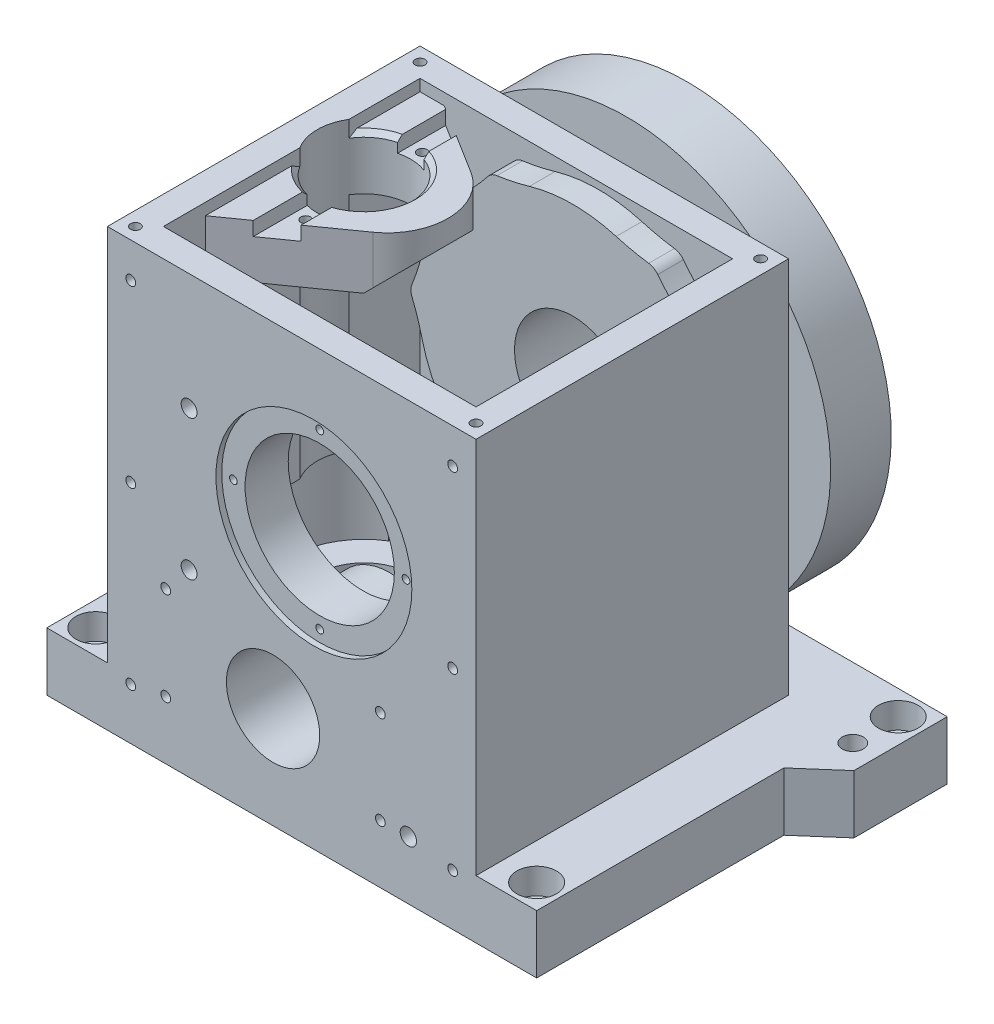
SolidWorks part; units mm, degrees
material "Ductile Iron"
ref_plane "Front Plane" through (0, 0, 0) normal (0, 0, 1) x (1, 0, 0)
ref_plane "Top Plane" through (0, 0, 0) normal (0, 1, 0) x (1, 0, 0)
ref_plane "Right Plane" through (0, 0, 0) normal (1, 0, 0) x (0, 0, -1)
sketch "Sketch1" plane through (0, 0, 0) normal (0, 0, 1) x (1, 0, 0)
  line L1 (79, -93.5) -> (-79, -93.5)
  line L2 (79, -93.5) -> (79, 93.5)
  line L3 (79, 93.5) -> (-79, 93.5)
  line L4 (-79, -93.5) -> (-79, 93.5)
  line L5 (79, -93.5) -> (-79, 93.5) construction
  line L6 (79, 93.5) -> (-79, -93.5) construction
  point P0 (0, 0)
  dimension "D1" = 158
  dimension "D2" = 187
extrude "Extrude1" add sketch "Sketch1" along normal blind 134
shell "Shell1" thickness 12 removed face at (0, 93.5, 67)
sketch "Sketch2" plane through (0, 0, 0) normal (0, 0, -1) x (-1, 0, 0)
  line L0 (-79, 93.5) -> (79, 93.5) construction
  line L1 (-79, -93.5) -> (-79, 93.5) construction
  circle A0 centre (-9.5, 24) radius 87.5
  dimension "D1" = 18
  dimension "D2" = 18
  dimension "D3" = 175
extrude "Extrude2" add sketch "Sketch2" along normal blind 26
sketch "Sketch3" plane through (0, 0, -26) normal (0, 0, -1) x (-1, 0, 0)
  circle A0 centre (-9.5, 24) radius 82.5
  circle A1 centre (-9.5, 24) radius 87.5 construction
  dimension "D1" = 5
extrude "Extrude4" cut sketch "Sketch3" against normal blind 11
sketch "Sketch4" plane through (0, 0, -15) normal (0, 0, -1) x (-1, 0, 0)
  circle A0 centre (-9.5, 24) radius 75.5
  circle A1 centre (-9.5, 24) radius 87.5 construction
  dimension "D1" = 12
extrude "Extrude5" cut sketch "Sketch4" against normal blind 5
sketch "Sketch5" plane through (0, 0, -10) normal (0, 0, -1) x (-1, 0, 0)
  circle A0 centre (-9.5, 24) radius 57
  dimension "D1" = 114
extrude "Extrude6" add sketch "Sketch5" along normal blind 18
sketch "Sketch6" plane through (0, 0, -28) normal (0, 0, -1) x (-1, 0, 0)
  circle A0 centre (-9.5, 24) radius 25
  dimension "D1" = 50
extrude "Extrude7" cut sketch "Sketch6" against normal blind 109
sketch "Sketch8" plane through (0, 0, 134) normal (0, 0, 1) x (1, 0, 0)
  circle A0 centre (9.5, 24) radius 32
  circle A1 centre (9.5, 24) radius 25 construction
  dimension "D1" = 64
extrude "Extrude8" cut sketch "Sketch8" against normal blind 109
sketch "Sketch41" plane through (0, 0, 122) normal (0, 0, -1) x (-1, 0, 0)
  circle A0 centre (-9.5, 24) radius 41
  circle A1 centre (-9.5, 24) radius 32 construction
  circle A2 centre (-9.5, 24) radius 32
  circle A3 centre (-9.5, 24) radius 32 construction
  dimension "D1" = 9
extrude "Extrude42" add sketch "Sketch41" along normal blind 9
sketch "Sketch9" plane through (0, 0, 134) normal (0, 0, 1) x (1, 0, 0)
  circle A0 centre (9.5, 24) radius 42
  circle A1 centre (9.5, 24) radius 32 construction
  dimension "D1" = 10
extrude "Extrude9" cut sketch "Sketch9" against normal blind 2.5
hole_wizard "M5 Tapped Hole7" positions "Sketch60" profile "Sketch59" tap size "M5" standard "ISO"
sketch "Sketch60" plane through (0, 0, -10) normal (0, 0, -1) x (-1, 0, 0)
  line L0 (-9.5, 99.5) -> (-9.5, -51.5) construction
  line L2 (-9.5, 24) -> (66, 24) construction
  line L4 (-9.5, 24) -> (-72.9, 24) construction
  circle A0 centre (-9.5, 24) radius 75.5 construction
  circle A1 centre (-9.5, 24) radius 75.5 construction
  circle A2 centre (-9.5, 24) radius 57 construction
  point P0 (-72.9, 24)
  dimension "D1" = 6.4
sketch "Sketch59" plane through (72.9, 24, -10) normal (1, 0, 0) x (0, 1, 0)
  line L0 (0, 0) -> (0, 23.2618)
  line L1 (0, 23.2618) -> (2.1, 22)
  line L2 (2.1, 22) -> (2.1, 0)
  line L5 (2.1, 0) -> (0, 0)
  line L10 (0, 23.2618) -> (-2.1, 22) construction
  line L11 (0, -6.35) -> (0, 107.95) construction
  dimension "Tap Drill Dia." = 4.2
  dimension "Tap Drill Depth" = 22
  dimension "Drill Angle" = 118
cosmetic thread "Hole Thread10" parameters "D1"=18, "D2"=5
pattern_circular "CirPattern7" count 6 every 60 about axis through (9.5, 24, -28) along (0, 0, -1) of "M5 Tapped Hole7"
sketch "Sketch10" plane through (0, 0, 134) normal (0, 0, 1) x (1, 0, 0)
  line L0 (-79, 93.5) -> (-79, -93.5) construction
  line L1 (-79, -93.5) -> (79, -93.5) construction
  circle A0 centre (-8, -50) radius 20
  dimension "D1" = 51
  dimension "D2" = 23.5
  dimension "D3" = 40
extrude "Extrude10" cut sketch "Sketch10" against normal blind 135.5
sketch "Sketch11" plane through (0, -93.5, 0) normal (0, -1, 0) x (1, 0, 0)
  line L0 (-79, 134) -> (79, 134) construction
  line L1 (105, 134) -> (79, 134)
  line L2 (105, 134) -> (105, -26)
  line L3 (105, -26) -> (-105, -26)
  line L4 (-105, 134) -> (-105, -26)
  line L5 (0, 0) -> (0, 134) construction
  line L7 (79, 0) -> (-79, 0)
  line L8 (79, 134) -> (79, 0)
  line L9 (-79, 0) -> (-79, 134)
  line L13 (79, 134) -> (79, 0) construction
  line L14 (-79, 134) -> (-105, 134)
  dimension "D1" = 210
  dimension "D2" = 160
  dimension "D3" = 26
extrude "Extrude12" add sketch "Sketch11" against normal blind 25
sketch "Sketch12" plane through (0, 0, -26) normal (0, 0, -1) x (-1, 0, 0)
  line L0 (-43.0857, -67) -> (24.0857, -67)
  arc A0 (-43.0857, -67) -> (24.0857, -67) centre (-9.5, 24) ccw
  dimension "D2" = 194
  dimension "D1" = 6
extrude "Extrude13" cut sketch "Sketch12" against normal up to surface (26 mm away) up to face at (-57.6084, -2.2759, 0)
sketch "Sketch13" plane through (0, 0, -28) normal (0, 0, -1) x (-1, 0, 0)
  line L0 (-9.5, 24) -> (-9.5, 88.8285) construction
  line L1 (-55, 24) -> (36, 24) construction
  line L3 (-56.5, 38.5) -> (-53.5, 38.5)
  line L4 (-56.5, 38.5) -> (-56.5, 32.3666)
  line L6 (-53.5, 38.5) -> (-53.5, 32.3666)
  arc A0 (-56.5, 32.3666) -> (-53.5, 32.3666) centre (-55, 24) ccw
  point P10 (-55, 38.5)
  dimension "D2" = 17
  dimension "D1" = 91
  dimension "D3" = 6
  dimension "D4" = 3
extrude "Extrude14" cut sketch "Sketch13" against normal blind 45
pattern_circular "CirPattern1" count 2 every 180 about axis through (9.5, 24, -28) along (0, 0, -1) of "Extrude14"
sketch "Sketch16" plane through (0, 0, -28) normal (0, 0, -1) x (-1, 0, 0)
  line L0 (-9.5, 81) -> (-9.5, 24) construction
  line L1 (-9.5, 24) -> (-40.5, 24) construction
  circle A0 centre (-40.5, 24) radius 4
  circle A1 centre (-9.5, 24) radius 57 construction
  circle A2 centre (-9.5, 24) radius 57 construction
  circle A6 centre (-9.5, 24) radius 25 construction
  dimension "D1" = 8
  dimension "D2" = 6
extrude "Extrude15" cut sketch "Sketch16" against normal blind 45
pattern_circular "CirPattern2" count 6 every 60 about axis through (9.5, 24, -28) along (0, 0, -1) of "Extrude15"
sketch "Sketch17" plane through (0, 0, -10) normal (0, 0, -1) x (-1, 0, 0)
  line L0 (-9.5, 24) -> (-106.9282, 24) construction
  line L1 (-9.5, 24) -> (-63.1936, 55) construction
  circle A0 centre (-63.1936, 55) radius 4
  circle A1 centre (-9.5, 24) radius 57 construction
  dimension "D2" = 8
  dimension "D3" = 1
  dimension "D1" = 30
extrude "Extrude16" cut sketch "Sketch17" against normal blind 21
sketch "Sketch18" plane through (0, 0, -10) normal (0, 0, -1) x (-1, 0, 0)
  line L0 (-9.5, 81) -> (-9.5, 24) construction
  line L1 (-9.5, 24) -> (-63.1936, -7) construction
  circle A0 centre (-9.5, 24) radius 57 construction
  circle A1 centre (-9.5, 24) radius 57 construction
  circle A2 centre (-63.1936, -7) radius 3
  dimension "D2" = 6
  dimension "D3" = 2
  dimension "D1" = 120
extrude "Extrude17" cut sketch "Sketch18" against normal blind 9
pattern_circular "CirPattern3" count 2 every 180 about axis through (9.5, 24, 81) along (0, 0, -1) of "Extrude16"
pattern_circular "CirPattern4" count 2 every 180 about axis through (9.5, 24, 81) along (0, 0, -1) of "Extrude17"
sketch "Sketch19" plane through (0, -68.5, 0) normal (0, 1, 0) x (1, 0, 0)
  line L0 (105, -28) -> (105, 26)
  line L1 (105, 26) -> (121, 26)
  line L2 (121, 26) -> (121, -14)
  line L3 (121, -14) -> (105, -28)
  line L4 (105, 26) -> (105, -134) construction
  dimension "D1" = 16
  dimension "D2" = 54
  dimension "D3" = 40
extrude "Extrude18" add sketch "Sketch19" against normal up to surface (25 mm away) up to face at (0, -93.5, 54)
sketch "Sketch20" plane through (0, -68.5, 0) normal (0, 1, 0) x (1, 0, 0)
  line L0 (-105, 26) -> (-19.7019, 26) construction
  line L1 (-105, -134) -> (-105, 26) construction
  line L2 (-79, -134) -> (-105, -134) construction
  line L3 (105, -28) -> (105, -134) construction
  line L4 (105, -134) -> (79, -134) construction
  line L5 (38.7019, 26) -> (121, 26) construction
  line L6 (121, -14) -> (121, 26) construction
  circle A0 centre (-94.5, -123.5) radius 8.5
  circle A1 centre (-94.5, 15.5) radius 8.5
  circle A2 centre (110.5, 15.5) radius 8.5
  circle A3 centre (94.5, -123.5) radius 8.5
  dimension "D1" = 17
  dimension "D2" = 10.5
  dimension "D3" = 10.5
  dimension "D4" = 10.5
  dimension "D5" = 10.5
  dimension "D6" = 10.5
  dimension "D7" = 10.5
  dimension "D8" = 10.5
  dimension "D9" = 10.5
extrude "Extrude19" cut sketch "Sketch20" against normal blind 11
sketch "Sketch21" plane through (0, -68.5, 0) normal (0, 1, 0) x (1, 0, 0)
  line L1 (38.7019, 26) -> (121, 26) construction
  circle A0 centre (-94.5, 15.5) radius 5.5
  circle A1 centre (-94.5, -123.5) radius 5.5
  circle A2 centre (94.5, -123.5) radius 5.5
  circle A3 centre (110.5, 15.5) radius 5.5
  circle A4 centre (110.5, -4) radius 4.5
  dimension "D1" = 11
  dimension "D2" = 9
  dimension "D3" = 30
extrude "Extrude20" cut sketch "Sketch21" against normal through all
sketch "Sketch22" plane through (0, 0, 12) normal (0, 0, 1) x (1, 0, 0)
  line L1 (67, 93.5) -> (-67, 93.5) construction
  line L2 (67, 57.4066) -> (67, -9.4066)
  line L3 (67, -81.5) -> (67, 93.5) construction
  line L5 (16.6041, -81.5) -> (-32.6041, -81.5)
  line L6 (-67, -81.5) -> (67, -81.5) construction
  arc A0 (67, 57.4066) -> (47.1987, 78.7819) centre (9.5, 24) ccw
  arc A1 (-37.5071, -23.0381) -> (-32.6041, -81.5) centre (-8, -50) ccw
  arc A2 (47.1987, 78.7819) -> (38.0932, 84.039) centre (41.2, 78.906) ccw
  circle A3 centre (9.5, 24) radius 25 construction
  arc A4 (30.4583, -39.111) -> (38.0932, -36.039) centre (9.5, 24) ccw
  arc A5 (16.6041, -81.5) -> (30.4583, -39.111) centre (-8, -50) ccw
  arc A6 (38.0932, 84.039) -> (-19.0932, 84.039) centre (9.5, 24) ccw
  arc A7 (-19.0932, 84.039) -> (-28.1987, 78.7819) centre (-22.2, 78.906) ccw
  arc A8 (-28.1987, 78.7819) -> (-56.7919, 29.2571) centre (9.5, 24) ccw
  arc A9 (38.0932, -36.039) -> (47.1987, -30.7819) centre (41.2, -30.906) ccw
  arc A10 (47.1987, -30.7819) -> (67, -9.4066) centre (9.5, 24) ccw
  arc A11 (-56.7919, 29.2571) -> (-56.7919, 18.7429) centre (-53.9, 24) ccw
  arc A12 (-56.7919, 18.7429) -> (-37.5071, -23.0381) centre (9.5, 24) ccw
  dimension "D1" = 3
  dimension "D2" = 39.9701
  dimension "D3" = 6
  dimension "D4" = 12
  dimension "D5" = 12
  dimension "D6" = 12
extrude "Extrude25" add sketch "Sketch22" along normal blind 11
sketch "Sketch23" plane through (0, 0, 23) normal (0, 0, 1) x (1, 0, 0)
  circle A0 centre (-8, -50) radius 20
  circle A1 centre (-8, -50) radius 20 construction
extrude "Extrude26" cut sketch "Sketch23" against normal blind 21
sketch "Sketch24" plane through (0, 0, 12) normal (0, 0, -1) x (-1, 0, 0)
  circle A0 centre (-9.5, 24) radius 25
  circle A1 centre (-9.5, 24) radius 25 construction
extrude "Extrude27" cut sketch "Sketch24" against normal blind 74
ref_plane "Plane1" through (0, 88.5, 0) normal (0, 1, 0) x (-1, 0, 0)
sketch "Sketch25" plane through (0, 88.5, 0) normal (0, 1, 0) x (-1, 0, 0)
  line L0 (67, 104) -> (24.9671, 74.2135)
  line L1 (67, 122) -> (67, 12) construction
  line L2 (67, 104) -> (67, 63.5357)
  line L3 (26.24, 30.9396) -> (56.6045, 12)
  line L4 (-67, 12) -> (67, 12) construction
  line L5 (67, 12) -> (56.6045, 12)
  line L7 (43.6601, 0) -> (79, 0) construction
  line L8 (67, 42.4643) -> (67, 12)
  arc A0 (24.9671, 74.2135) -> (26.24, 30.9396) centre (40, 53) ccw
  arc A1 (67, 63.5357) -> (67, 42.4643) centre (50, 53) ccw
  dimension "D2" = 53
  dimension "D3" = 26
  dimension "D6" = 40
  dimension "D1" = 92
  dimension "D4" = 53
  dimension "D5" = 67.277
  dimension "D7" = 10
extrude "Extrude28" add sketch "Sketch25" against normal blind 23
ref_plane "Plane2" through (0, 0, 97) normal (0, 0, 1) x (1, 0, 0)
sketch "Sketch26" plane through (0, 0, 97) normal (0, 0, 1) x (1, 0, 0)
  line L0 (-14.3015, 78.5) -> (-44, 48.8015)
  line L1 (73.7, 88.5) -> (-73.7, 88.5) construction
  line L2 (-67, 65.5) -> (-67, -81.5) construction
  line L3 (-14.3015, 78.5) -> (-10.4023, 82.3992)
  line L4 (-10.4023, 82.3992) -> (-10.4023, 48.8015)
  line L5 (-10.4023, 48.8015) -> (-44, 48.8015)
  dimension "D1" = 45
  dimension "D2" = 10
  dimension "D3" = 23
  dimension "D4" = 42
  dimension "D5" = 33.5977
extrude "Extrude29" cut sketch "Sketch26" against normal blind 73
sketch "Sketch28" plane through (0, -93.5, 0) normal (0, -1, 0) x (1, 0, 0)
  line L0 (-50, 83) -> (-79, 83)
  line L1 (-79, 134) -> (-79, 0) construction
  line L2 (-79, 23) -> (-50, 23)
  arc A0 (-50, 23) -> (-50, 83) centre (-50, 53) ccw
  arc A1 (-79, 83) -> (-79, 23) centre (-50, 53) ccw
  arc A2 (-67, 42.4643) -> (-67, 63.5357) centre (-50, 53) ccw construction
  dimension "D4" = 60
extrude "Extrude36" add sketch "Sketch28" against normal blind 74
sketch "Sketch36" plane through (0, -19.5, 0) normal (0, 1, 0) x (1, 0, 0)
  line L0 (-50, -23) -> (-67, -23)
  line L1 (-50, -83) -> (-67, -83)
  line L3 (-67, -23) -> (-67, -83)
  line L4 (-67, -83) -> (-67, -23) construction
  arc A0 (-50, -83) -> (-50, -23) centre (-50, -53) ccw
  arc A1 (-50, -83) -> (-50, -23) centre (-50, -53) ccw construction
extrude "Extrude37" cut sketch "Sketch36" against normal blind 52
sketch "Sketch37" plane through (0, -71.5, 0) normal (0, 1, 0) x (1, 0, 0)
  line L0 (-50, -23) -> (-50, -83)
  line L2 (-67, -83) -> (-50, -83) construction
  line L3 (-50, -83) -> (-62.0473, -83)
  line L4 (-50, -23) -> (-62.0473, -23)
  line L5 (47.1987, -23) -> (67, -23) construction
  line L6 (-50, -23) -> (-67, -23) construction
  arc A0 (-62.0473, -23) -> (-62.0473, -83) centre (-50, -53) ccw
  arc A2 (-50, -83) -> (-50, -23) centre (-50, -53) ccw construction
  arc A4 (-79, -23) -> (-79, -83) centre (-50, -53) ccw construction
  dimension "D1" = 9.3967
extrude "Extrude38" cut sketch "Sketch37" along normal blind 42
sketch "Sketch38" plane through (0, 0, 134) normal (0, 0, 1) x (1, 0, 0)
  line L0 (-79, -19.5) -> (-97.6698, -38.1698)
  line L1 (-97.6698, -38.1698) -> (-97.6698, -9.9037)
  line L2 (-97.6698, -9.9037) -> (-79, -19.5)
  line L4 (-79, 93.5) -> (-79, -68.5) construction
  dimension "D1" = 45
  dimension "D2" = 62.797
  dimension "D3" = 28.2661
extrude "Extrude39" cut sketch "Sketch38" against normal blind 154
sketch "Sketch35" plane through (0, 88.5, 0) normal (0, 1, 0) x (1, 0, 0)
  circle A0 centre (-50, -53) radius 20
  arc A2 (-67, -63.5357) -> (-67, -42.4643) centre (-50, -53) ccw construction
extrude "Extrude35" cut sketch "Sketch35" against normal blind 239
sketch "Sketch39" plane through (0, -93.5, 0) normal (0, -1, 0) x (1, 0, 0)
  circle A0 centre (-50, 53) radius 30
  dimension "D1" = 60
extrude "Extrude40" cut sketch "Sketch39" against normal blind 7
sketch "Sketch40" plane through (0, -93.5, 0) normal (0, -1, 0) x (1, 0, 0)
  line L0 (-70, 117) -> (75, 117)
  line L1 (75, 117) -> (75, 7)
  line L2 (75, 7) -> (-50, 7)
  line L3 (-50, 7) -> (-50, 13)
  line L4 (-70, 117) -> (-70, 93)
  line L5 (-70, 93) -> (-50, 93)
  line L6 (-105, -26) -> (121, -26) construction
  line L7 (105, 28) -> (105, 134) construction
  arc A0 (-50, 93) -> (-50, 13) centre (-50, 53) cw
  circle A2 centre (-50, 53) radius 30 construction
  dimension "D1" = 40
  dimension "D2" = 33
  dimension "D3" = 110
  dimension "D4" = 145
  dimension "D5" = 30
extrude "Extrude41" cut sketch "Sketch40" against normal blind 3
chamfer "Chamfer1" distance 3 angle 45 7 edges at (2.5, -90.5, 117) (75, -90.5, 62) (12.5, -90.5, 7) (-50, -90.5, 10) (-10, -90.5, 53) (-60, -90.5, 93) (-70, -90.5, 105)
sketch "Sketch42" plane through (0, 0, 122) normal (0, 0, -1) x (-1, 0, 0)
  line L0 (-17.5, -50) -> (-17.5, -81.5)
  line L1 (67, -81.5) -> (-67, -81.5) construction
  line L2 (33.5, -50) -> (33.5, -81.5)
  line L3 (33.5, -81.5) -> (-17.5, -81.5)
  arc A0 (33.5, -50) -> (-17.5, -50) centre (8, -50) ccw
  circle A1 centre (8, -50) radius 20
  circle A2 centre (8, -50) radius 20 construction
  dimension "D1" = 51
extrude "Extrude43" add sketch "Sketch42" along normal blind 38
sketch "Sketch43" plane through (0, 93.5, 0) normal (0, 1, 0) x (1, 0, 0)
  line L1 (-55, -13.0008) -> (-43, -13.0008)
  line L2 (-55, -13.0008) -> (-55, -95.4962)
  line L3 (-55, -95.4962) -> (-43, -95.4962)
  line L4 (-43, -13.0008) -> (-43, -95.4962)
  line L5 (-67, -12) -> (-67, -42.4643) construction
  line L6 (-67, -104) -> (-24.9671, -74.2135) construction
  line L7 (-26.24, -30.9396) -> (-56.6045, -12) construction
  dimension "D1" = 12
  dimension "D2" = 12
extrude "Extrude44" cut sketch "Sketch43" against normal blind 11
sketch "Sketch44" plane through (0, 82.5, 0) normal (0, 1, 0) x (1, 0, 0)
  circle A0 centre (-50, -53) radius 20
  arc A1 (-55, -33.6351) -> (-67, -42.4643) centre (-50, -53) ccw construction
extrude "Cut-Extrude1" cut sketch "Sketch44" along normal blind 50
chamfer "Chamfer2" distance 2 angle 45 3 edges at (-61.8528, 88.5, 69.1093) (-30, 88.5, 53) (-61.8528, 88.5, 36.8907)
hole_wizard "M5 Tapped Hole1" positions "Sketch47" profile "Sketch46" tap size "M5" standard "ISO"
sketch "Sketch47" plane through (0, 93.5, 0) normal (0, 1, 0) x (-1, 0, 0)
  line L0 (43.6601, 0) -> (79, 0) construction
  line L1 (79, 134) -> (79, 0) construction
  point P0 (73, 6)
  dimension "D1" = 6
  dimension "D2" = 6
sketch "Sketch46" plane through (-73, 93.5, 6) normal (1, 0, 0) x (0, 0, 1)
  line L0 (0, 0) -> (0, 15.2618)
  line L1 (0, 15.2618) -> (2.1, 14)
  line L2 (2.1, 14) -> (2.1, 0)
  line L5 (2.1, 0) -> (0, 0)
  line L10 (0, 15.2618) -> (-2.1, 14) construction
  line L11 (0, -6.35) -> (0, 107.95) construction
  dimension "Tap Drill Dia." = 4.2
  dimension "Tap Drill Depth" = 14
  dimension "Drill Angle" = 118
cosmetic thread "Hole Thread1" parameters "D1"=10, "D2"=5
pattern_linear "LPattern1" count 2 spacing 146 along (1, 0, 0) count 2 spacing 122 along (0, 0, 1) of "M5 Tapped Hole1"
hole_wizard "M5 Tapped Hole2" positions "3DSketch1" profile "Sketch48" tap size "M5" standard "ISO"
sketch3d "3DSketch1"
  line L0 (79, 93.5, 134) -> (-79, 93.5, 134) construction
  line L1 (-79, 93.5, 134) -> (-79, -68.5, 134) construction
  point P0 (-69, 78.5, 134)
  dimension "D1" = 15
  dimension "D2" = 10
sketch "Sketch48" plane through (-69, 78.5, 134) normal (1, 0, 0) x (0, -1, 0)
  line L0 (0, 0) -> (0, 10.2618)
  line L1 (0, 10.2618) -> (2.1, 9)
  line L2 (2.1, 9) -> (2.1, 0)
  line L5 (2.1, 0) -> (0, 0)
  line L10 (0, 10.2618) -> (-2.1, 9) construction
  line L11 (0, -6.35) -> (0, 107.95) construction
  dimension "Tap Drill Dia." = 4.2
  dimension "Tap Drill Depth" = 9
  dimension "Drill Angle" = 118
cosmetic thread "Hole Thread2" parameters "D1"=5, "D2"=5
pattern_linear "LPattern2" count 3 spacing 75 along (0, -1, 0) count 2 spacing 138 along (1, 0, 0) of "M5 Tapped Hole2"
hole_wizard "M8 Tapped Hole1" positions "3DSketch2" profile "Sketch49" tap size "M8" standard "ISO"
sketch3d "3DSketch2"
  line L0 (79, 93.5, 134) -> (-79, 93.5, 134) construction
  line L1 (-79, 93.5, 134) -> (-79, -68.5, 134) construction
  point P0 (-44, 43.5, 134)
  dimension "D1" = 50
  dimension "D2" = 35
sketch "Sketch49" plane through (-44, 43.5, 134) normal (1, 0, 0) x (0, -1, 0)
  line L0 (0, 0) -> (0, 10.0429)
  line L1 (0, 10.0429) -> (3.4, 8)
  line L2 (3.4, 8) -> (3.4, 0)
  line L5 (3.4, 0) -> (0, 0)
  line L10 (0, 10.0429) -> (-3.4, 8) construction
  line L11 (0, -6.35) -> (0, 107.95) construction
  dimension "Tap Drill Dia." = 6.8
  dimension "Tap Drill Depth" = 8
  dimension "Drill Angle" = 118
cosmetic thread "Hole Thread3" parameters "D1"=7, "D2"=8
pattern_linear "LPattern3" count 2 spacing 60 along (0, -1, 0) of "M8 Tapped Hole1"
hole_wizard "M5 Tapped Hole3" positions "3DSketch3" profile "Sketch50" tap size "M5" standard "ISO"
sketch3d "3DSketch3"
  line L0 (-105, -93.5, 134) -> (105, -93.5, 134) construction
  line L2 (-79, 93.5, 134) -> (-79, -68.5, 134) construction
  point P0 (-54, -68.5, 134)
  dimension "D1" = 25
  dimension "D2" = 25
sketch "Sketch50" plane through (-54, -68.5, 134) normal (1, 0, 0) x (0, -1, 0)
  line L0 (0, 0) -> (0, 10.2618)
  line L1 (0, 10.2618) -> (2.1, 9)
  line L2 (2.1, 9) -> (2.1, 0)
  line L5 (2.1, 0) -> (0, 0)
  line L10 (0, 10.2618) -> (-2.1, 9) construction
  line L11 (0, -6.35) -> (0, 107.95) construction
  dimension "Tap Drill Dia." = 4.2
  dimension "Tap Drill Depth" = 9
  dimension "Drill Angle" = 118
cosmetic thread "Hole Thread4" parameters "D1"=5, "D2"=5
pattern_linear "LPattern4" count 2 spacing 40 along (0, 1, 0) count 2 spacing 92 along (1, 0, 0) of "M5 Tapped Hole3"
sketch "Sketch52" plane through (0, 0, 134) normal (0, 0, 1) x (1, 0, 0)
  circle A0 centre (50, -68.5) radius 3.5
  dimension "D1" = 7
  dimension "D2" = 12
extrude "Cut-Extrude2" cut sketch "Sketch52" against normal blind 10
hole_wizard "M4 Tapped Hole1" positions "3DSketch4" profile "Sketch54" tap size "M4" standard "ISO"
sketch3d "3DSketch4"
  line L3 (9.5, 24, 23) -> (9.5, 61, 23) construction
  line L4 (9.5, 24, 23) -> (9.5, 24, -28) construction
  point P14 (9.5, 61, 131.5)
  dimension "D1" = 37
sketch "Sketch54" plane through (9.5, 61, 131.5) normal (1, 0, 0) x (0, -1, 0)
  line L0 (0, 0) -> (0, 10.9914)
  line L1 (0, 10.9914) -> (1.65, 10)
  line L2 (1.65, 10) -> (1.65, 0)
  line L5 (1.65, 0) -> (0, 0)
  line L10 (0, 10.9914) -> (-1.65, 10) construction
  line L11 (0, -6.35) -> (0, 107.95) construction
  dimension "Tap Drill Dia." = 3.3
  dimension "Tap Drill Depth" = 10
  dimension "Drill Angle" = 118
cosmetic thread "Hole Thread5" parameters "D1"=8, "D2"=4
pattern_circular "CirPattern5" count 4 every 90 about axis through (9.5, 24, 134) along (0, 0, 1) of "M4 Tapped Hole1"
hole_wizard "M5 Tapped Hole5" positions "3DSketch6" profile "Sketch57" tap size "M5" standard "ISO"
sketch3d "3DSketch6"
  line L0 (-50, -86.5, 53) -> (-25, -86.5, 53) construction
  line L1 (-50, -86.5, 53) -> (-50, -71.5, 53) construction
  circle A0 centre (-50, -86.5, 53) radius 20 construction
  point P7 (-25, -86.5, 53)
  point P13 (-50, -66.5, 53)
  dimension "D1" = 5
sketch "Sketch57" plane through (-25, -86.5, 53) normal (1, 0, 0) x (0, 0, -1)
  line L0 (0, 0) -> (0, 35.2618)
  line L1 (0, 35.2618) -> (2.1, 34)
  line L2 (2.1, 34) -> (2.1, 0)
  line L5 (2.1, 0) -> (0, 0)
  line L10 (0, 35.2618) -> (-2.1, 34) construction
  line L11 (0, -6.35) -> (0, 107.95) construction
  dimension "Tap Drill Dia." = 4.2
  dimension "Tap Drill Depth" = 34
  dimension "Drill Angle" = 118
cosmetic thread "Hole Thread7" parameters "D1"=15, "D2"=5
pattern_circular "CirPattern6" count 4 every 90 about axis through (-50, -86.5, 53) along (0, 1, 0) of "M5 Tapped Hole5"
hole_wizard "M5 Tapped Hole6" positions "3DSketch7" profile "Sketch58" tap size "M5" standard "ISO"
sketch3d "3DSketch7"
  line L0 (-50, 86.5, 53) -> (-50, 86.5, 78) construction
  line L2 (-50, 86.5, 53) -> (-50, 86.5, 28) construction
  arc A0 (-43, 86.5, 71.735) -> (-43, 86.5, 34.265) centre (-50, 86.5, 53) ccw construction
  point P0 (-50, 82.5, 78)
  point P2 (-50, 82.5, 28)
  point P10 (-50, 106.5, 53)
  dimension "D1" = 25
  dimension "D2" = 25
sketch "Sketch58" plane through (-50, 82.5, 78) normal (1, 0, 0) x (0, 0, 1)
  line L0 (0, 0) -> (0, 35.2618)
  line L1 (0, 35.2618) -> (2.1, 34)
  line L2 (2.1, 34) -> (2.1, 0)
  line L5 (2.1, 0) -> (0, 0)
  line L10 (0, 35.2618) -> (-2.1, 34) construction
  line L11 (0, -6.35) -> (0, 107.95) construction
  dimension "Tap Drill Dia." = 4.2
  dimension "Tap Drill Depth" = 34
  dimension "Drill Angle" = 118
cosmetic thread "Hole Thread8" parameters "D1"=17, "D2"=5
cosmetic thread "Hole Thread9" parameters "D1"=17, "D2"=5
fillet "Fillet1" radius 100 8 edges at (38.0932, -36.039, 17.5) (47.1987, -30.7819, 17.5) (-56.7919, 18.7429, 17.5) (-56.7919, 29.2571, 17.5) (-28.1987, 78.7819, 17.5) (47.1987, 78.7819, 17.5) (-19.0932, 84.039, 17.5) (38.0932, 84.039, 17.5)
fillet "Fillet2" radius 10 1 edges at (30.4583, -39.111, 17.5)
sketch "Sketch62" plane through (0, 0, 12) normal (0, 0, -1) x (-1, 0, 0)
  circle A0 centre (-55, 24) radius 8.5
  circle A1 centre (36, 24) radius 8.5
  arc A2 (-56.5, 32.3666) -> (-53.5, 32.3666) centre (-55, 24) ccw construction
  arc A3 (37.5, 15.6334) -> (34.5, 15.6334) centre (36, 24) ccw construction
extrude "Cut-Extrude3" cut sketch "Sketch62" against normal blind 5
hole_wizard "M5 Tapped Hole9" positions "Sketch64" profile "Sketch63" tap size "M5" standard "ISO"
sketch "Sketch64" plane through (0, 93.5, 0) normal (0, 1, 0) x (-1, 0, 0)
  line L0 (-50.5, 122) -> (-50.5, 113) construction
  line L3 (-50.5, 122) -> (31.5, 122) construction
  point P0 (-9.5, 117.5)
  dimension "D1" = 41
  dimension "D2" = 4.5
sketch "Sketch63" plane through (9.5, 93.5, 117.5) normal (1, 0, 0) x (0, 0, 1)
  line L0 (0, 0) -> (0, 53.2618)
  line L1 (0, 53.2618) -> (2.1, 52)
  line L2 (2.1, 52) -> (2.1, 0)
  line L5 (2.1, 0) -> (0, 0)
  line L10 (0, 53.2618) -> (-2.1, 52) construction
  line L11 (0, -6.35) -> (0, 107.95) construction
  dimension "Tap Drill Dia." = 4.2
  dimension "Tap Drill Depth" = 52
  dimension "Drill Angle" = 118
cosmetic thread "Hole Thread11" parameters "D1"=37.569, "D2"=5
